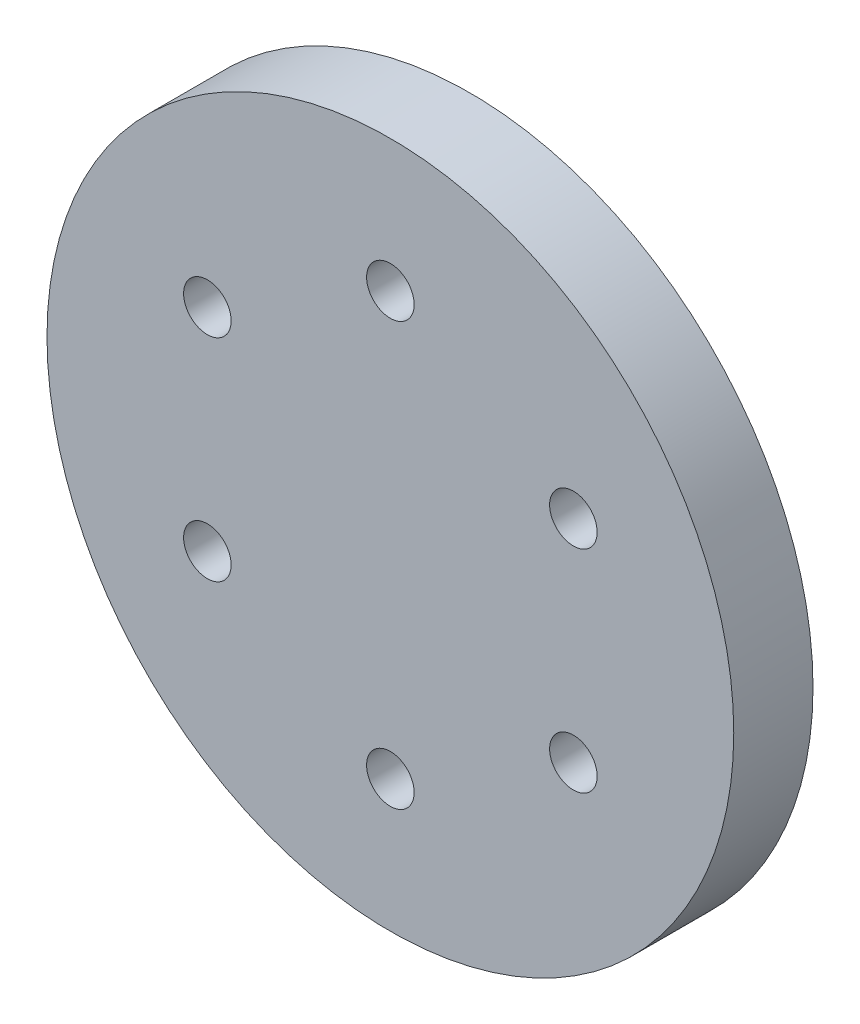
SolidWorks part; units mm, degrees
ref_plane "前视基准面" through (0, 0, 0) normal (0, 0, 1) x (1, 0, 0)
ref_plane "上视基准面" through (0, 0, 0) normal (0, 1, 0) x (1, 0, 0)
ref_plane "右视基准面" through (0, 0, 0) normal (1, 0, 0) x (0, 0, -1)
other "Configuration Table"
sketch "草图1" plane through (0, 0, 0) normal (0, 0, 1) x (1, 0, 0)
  circle A0 centre (0, 0) radius 13
  dimension "D1" = 26
extrude "凸台-拉伸1" add sketch "草图1" along normal blind 3 contours A0
sketch "草图2" plane through (0, 0, 0) normal (0, 0, -1) x (-1, 0, 0)
  circle A0 centre (0, 8) radius 1.5
  circle A1 centre (0, 8) radius 0.9
  point P3 (0, 0)
  dimension "D1" = 3
  dimension "D2" = 1.8
  dimension "D3" = 8
extrude "切除-拉伸1" cut sketch "草图2" against normal through all contours A1
extrude "切除-拉伸2" cut sketch "草图2<3>" against normal blind 1.5 contours A0
sketch "草图2<3>" plane through (0, 0, 0) normal (0, 0, -1) x (-1, 0, 0) same geometry as "草图2"
pattern_circular "阵列(圆周)1" count 6 over 360 about axis through (0, 0, 3) along (0, 0, -1) of "切除-拉伸1", "切除-拉伸2" reverse direction yes
